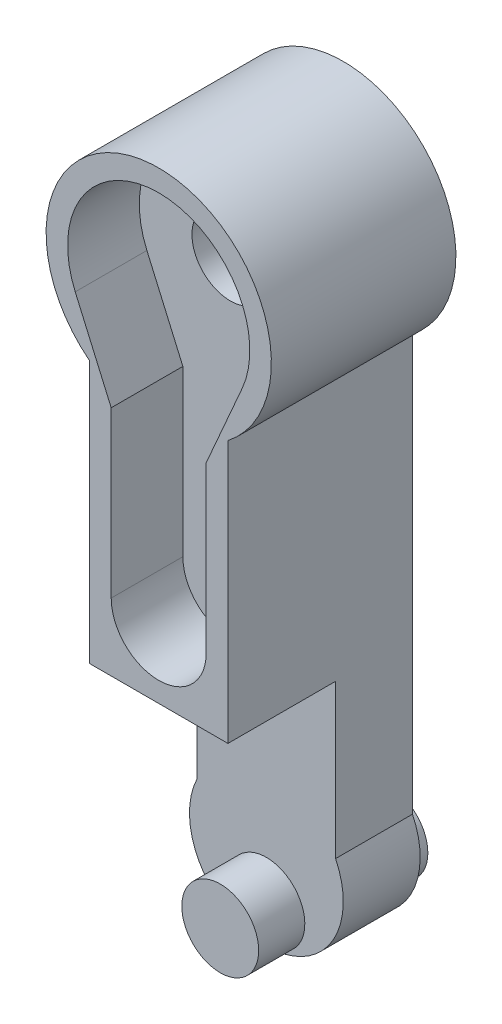
SolidWorks part; units mm, degrees
ref_plane "Front Plane" through (0, 0, 0) normal (0, 0, 1) x (1, 0, 0)
ref_plane "Top Plane" through (0, 0, 0) normal (0, 1, 0) x (1, 0, 0)
ref_plane "Right Plane" through (0, 0, 0) normal (1, 0, 0) x (0, 0, -1)
sketch "Sketch1" plane through (0, 0, 0) normal (0, 0, 1) x (1, 0, 0)
  line L0 (-5.715, 0) -> (-5.715, -41.6821)
  line L1 (5.715, 0) -> (5.715, -41.6821)
  line L2 (-5.715, -44.45) -> (5.715, -44.45) construction
  line L3 (-5.715, -41.6821) -> (-5.715, -44.45) construction
  line L4 (5.715, -41.6821) -> (5.715, -44.45) construction
  circle A0 centre (0, 0) radius 3.175
  arc A1 (5.715, 0) -> (-5.715, 0) centre (0, 0) ccw
  arc A2 (-5.715, -41.6821) -> (5.715, -41.6821) centre (0, -44.45) ccw
  arc A3 (5.715, -41.6821) -> (-5.715, -41.6821) centre (0, -44.45) ccw construction
  dimension "D1" = 6.35
  dimension "D4" = 12.7
  dimension "D2" = 11.43
  dimension "D3" = 44.45
extrude "Boss-Extrude1" add sketch "Sketch1" along normal blind 6.35
sketch "Sketch2" plane through (0, 0, 6.35) normal (0, 0, 1) x (1, 0, 0)
  circle A0 centre (0, -47.625) radius 3.175
  dimension "D1" = 6.35
  dimension "1.85" = 47.625
extrude "Boss-Extrude2" add sketch "Sketch2" along normal blind 3.81
extrude "Boss-Extrude3" add sketch "Sketch2<2>" against normal blind 3.81 from surface starting at face at (0, -21.6918, 0)
sketch "Sketch2<2>" plane through (0, 0, 6.35) normal (0, 0, 1) x (1, 0, 0) same geometry as "Sketch2"
sketch "Sketch4" plane through (0, 0, 6.35) normal (0, 0, 1) x (1, 0, 0)
  line L1 (-3.9243, -23.426) -> (-3.9243, -9.8157)
  line L2 (3.9243, -23.426) -> (3.9243, -9.8157)
  line L3 (-3.9243, -9.8157) -> (-6.8954, -3.0104)
  line L4 (3.7973, -23.426) -> (3.7973, -9.6604) construction
  line L5 (-3.7973, -9.6604) -> (-3.7973, -23.426) construction
  line L6 (3.9243, -9.8157) -> (6.8954, -3.0104)
  line L7 (5.715, -7.3392) -> (5.715, -29.0013)
  line L8 (5.715, -41.6821) -> (5.715, 0) construction
  line L9 (5.715, -29.0013) -> (-5.715, -29.0013)
  line L10 (-5.715, 0) -> (-5.715, -41.6821) construction
  line L11 (-5.715, -29.0013) -> (-5.715, -7.3392)
  arc A0 (-3.9243, -23.426) -> (3.9243, -23.426) centre (0, -23.426) ccw
  arc A1 (-3.7973, -23.426) -> (3.7973, -23.426) centre (0, -23.426) ccw construction
  arc A2 (6.8954, -3.0104) -> (-6.8954, -3.0104) centre (0, 0) ccw
  arc A3 (5.5933, -4.8403) -> (-5.5933, -4.8403) centre (0, 0) ccw construction
  arc A5 (5.715, -7.3392) -> (-5.715, -7.3392) centre (0, 0) ccw
  point P10 (0, -27.2233)
  point P11 (0, -27.3503)
  point P15 (0, 7.3969)
  point P16 (0, 7.5239)
  point P19 (0, 9.3019)
  point P31 (0, 0)
  line M8 (5.715, -41.6821) -> (5.715, 0)
  arc M9 (5.715, 0) -> (-5.715, 0) centre (0, 0) ccw
  line M10 (-5.715, 0) -> (-5.715, -41.6821)
  circle M11 centre (0, 0) radius 3.175
  dimension "D4" = 0.127
  dimension "D2" = 0.127
  dimension "D1" = 0.127
  dimension "D5" = 0.127
  dimension "D6" = 1.778
  dimension "D7" = 1.778
extrude "Boss-Extrude4" add sketch "Sketch4" along normal blind 8.89
extrude "Boss-Extrude6" add sketch "Sketch4<3>" against normal up to surface (6.35 mm away) contours L6 A2 L3 M10 M9 M8 | A5 L3 A2 L6 M8 M10 | A0 L1 L3 L9 L6 L2 M10 M8 region at (0, -27.6097, 6.35) region at (-5.9646, -6.5266, 6.35) region at (-6.1215, -4.2821, 6.35) up to face at (0.5292, -29.8728, 0)
sketch "Sketch4<3>" plane through (0, 0, 6.35) normal (0, 0, 1) x (1, 0, 0) same geometry as "Sketch4"
extrude "Boss-Extrude7" add sketch "Sketch4<4>" along normal offset from surface (2.9718 mm away) 5.9182 contours L1 A0 L2 L6 L3 M8 M9 M10 M11 | L6 A2 L3 M10 M9 M8 region at (0, -10.75, 6.35) region at (-6.1215, -4.2821, 6.35) up to face at (0, -14.01, 15.24)
sketch "Sketch4<4>" plane through (0, 0, 6.35) normal (0, 0, 1) x (1, 0, 0) same geometry as "Sketch4"
